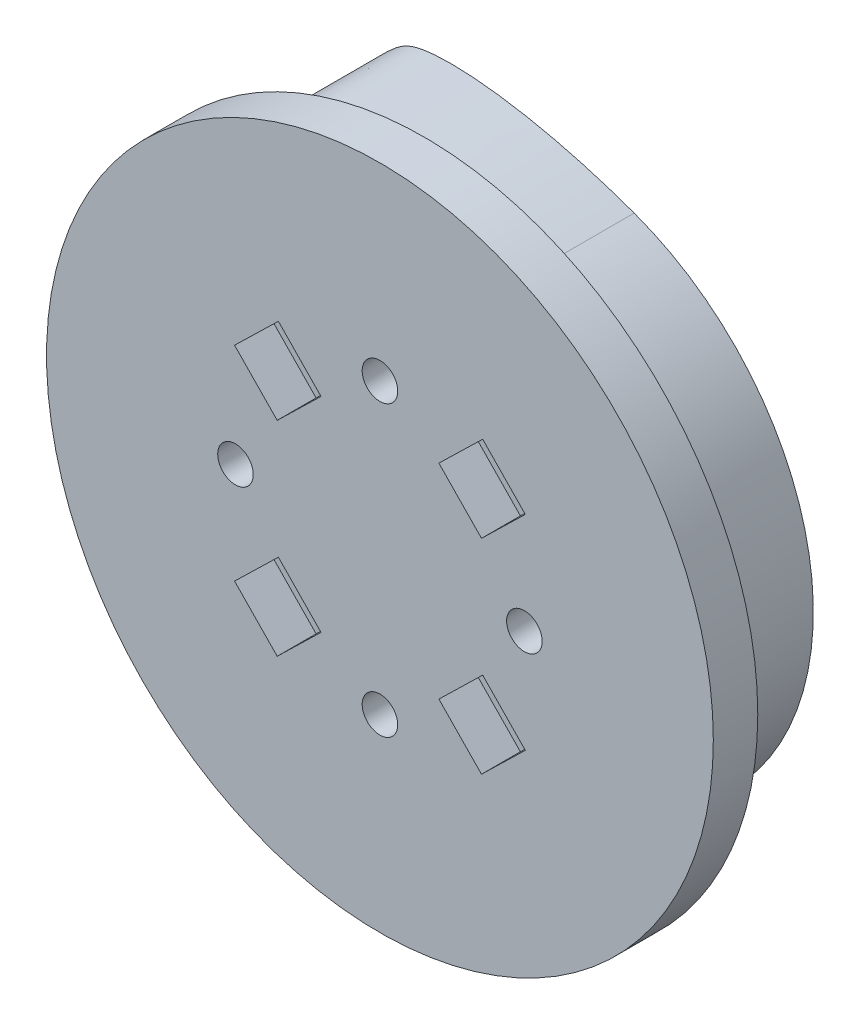
SolidWorks part; units mm, degrees
ref_plane "Front Plane" through (0, 0, 0) normal (1, 0, 0) x (0, 1, 0)
ref_plane "Top Plane" through (0, 0, 0) normal (0, 0, 1) x (0, 1, 0)
ref_plane "Right Plane" through (0, 0, 0) normal (0, 1, 0) x (-1, 0, 0)
sketch "Sketch1" plane through (0, 0, 0) normal (0, 0, 1) x (0, 1, 0)
  circle A0 centre (0, 0) radius 21
  circle A1 centre (0, 0) radius 13 construction
  circle A2 centre (0, 13) radius 1.6
  circle A3 centre (0, 13) radius 2.85
  circle A4 centre (13, 0) radius 2.85
  circle A5 centre (13, 0) radius 1.6
  circle A6 centre (0, -13) radius 2.85
  circle A7 centre (0, -13) radius 1.6
  circle A8 centre (-13, 0) radius 2.85
  circle A9 centre (-13, 0) radius 1.6
  point P19 (0, 0)
  dimension "D1" = 42
  dimension "D2" = 26
  dimension "D3" = 3.2
  dimension "D4" = 5.7
  dimension "D5" = 4
extrude "Boss-Extrude1" add sketch "Sketch1" along normal blind 10.5 contours A0 A8 A6 A4 A3 | A8 A9 | A3 A2 | A4 A5 | A6 A7 region at (0, 0, 0) region at (-13, -2.7694, 0) region at (0, 10.2306, 0) region at (13, -2.7694, 0) region at (0, -15.7694, 0)
sketch "Sketch2" plane through (0, 0, 0) normal (0, 0, -1) x (1, 0, 0)
  line L0 (0, 0) -> (0, 28.5) construction
  line L1 (0, 0) -> (-12.0446, -25.8298) construction
  line L2 (0, 0) -> (-26.7812, -9.7476) construction
  line L3 (0, 0) -> (9.7476, -26.7812) construction
  line L4 (-13.7052, -25.0554) -> (-49.9575, -8.1507) construction
  line L5 (-8.9203, -47.1248) -> (-49.9627, 65.6383) construction
  line L6 (47.1248, -8.9203) -> (-65.6383, -49.9627) construction
  circle A0 centre (0, 0) radius 28.5 construction
  circle A1 centre (0, 0) radius 24.5
  spline S0 degree 3 poles (-23.0225, -8.3795) (-19.9443, -16.8367) (-14.7237, -24.6248) (-9.3995, -27.1075) (-0.0777, -26.1007) (8.3795, -23.0225) knots 0 0 0 0 0.45 0.55 1 1 1 1
  circle M5 centre (0, 0) radius 21
  dimension "D1" = 57
  dimension "D2" = 49
  dimension "D6" = 20
  dimension "D7" = 30
  dimension "D8" = 30
  dimension "D3" = 205
  dimension "D4" = 45
  dimension "D5" = 45
  dimension "D9" = 90
  dimension "D10" = 90
  dimension "D11" = 90
extrude "Boss-Extrude3" add sketch "Sketch2" against normal up to surface (10.5 mm away) contours A1 M5 | A1 S0 region at (19.5016, 13.6552, 0) region at (-10.6097, 22.7453, 0) up to face at (21, 0, 10.5)
sketch "Sketch4" plane through (0, 0, 10.5) normal (0, 0, 1) x (1, 0, 0)
  circle A0 centre (0, 0) radius 30
  circle A5 centre (-13, 0) radius 1.6
  circle A6 centre (0, 13) radius 1.6
  circle A7 centre (13, 0) radius 1.6
  circle A8 centre (0, -13) radius 1.6
  dimension "D1" = 60
extrude "Boss-Extrude5" add sketch "Sketch4" along normal blind 4
sketch "Sketch3" plane through (0, 0, 0) normal (0, 0, -1) x (1, 0, 0)
  circle A0 centre (0, 0) radius 21
  circle A5 centre (-13, 0) radius 1.6
  circle A6 centre (0, 13) radius 1.6
  circle A7 centre (13, 0) radius 1.6
  circle A8 centre (0, -13) radius 1.6
  dimension "D1" = 42
extrude "Boss-Extrude4" add sketch "Sketch3" along normal blind 0.5
sketch "Sketch6" plane through (0, 0, -0.5) normal (0, 0, -1) x (1, 0, 0)
  line L0 (15.75, -2.75) -> (10.25, -2.75)
  line L1 (-2.75, 15.75) -> (2.75, 15.75)
  line L2 (-2.75, 15.75) -> (-2.75, 10.25)
  line L3 (-2.75, 10.25) -> (2.75, 10.25)
  line L4 (2.75, 15.75) -> (2.75, 10.25)
  line L5 (-2.75, 15.75) -> (2.75, 10.25) construction
  line L6 (-2.75, 10.25) -> (2.75, 15.75) construction
  line L7 (10.25, 2.75) -> (10.25, -2.75)
  line L8 (15.75, 2.75) -> (10.25, 2.75)
  line L9 (15.75, 2.75) -> (15.75, -2.75)
  line L10 (15.75, 2.75) -> (10.25, -2.75) construction
  line L11 (10.25, 2.75) -> (15.75, -2.75) construction
  line L12 (-2.75, -15.75) -> (-2.75, -10.25)
  line L13 (2.75, -10.25) -> (-2.75, -10.25)
  line L14 (2.75, -15.75) -> (2.75, -10.25)
  line L15 (2.75, -15.75) -> (-2.75, -15.75)
  line L16 (2.75, -15.75) -> (-2.75, -10.25) construction
  line L17 (2.75, -10.25) -> (-2.75, -15.75) construction
  line L18 (-15.75, 2.75) -> (-10.25, 2.75)
  line L19 (-10.25, -2.75) -> (-10.25, 2.75)
  line L20 (-15.75, -2.75) -> (-10.25, -2.75)
  line L21 (-15.75, -2.75) -> (-15.75, 2.75)
  line L22 (-15.75, -2.75) -> (-10.25, 2.75) construction
  line L23 (-10.25, -2.75) -> (-15.75, 2.75) construction
  point P0 (0, 13)
  point P21 (0, 0)
  dimension "D1" = 5.5
  dimension "D2" = 5.5
extrude "Cut-Extrude2" cut sketch "Sketch6" against normal offset from surface (3.5 mm away) 11.5 up to face at (14.6, 0, 14.5)
sketch "Sketch7" plane through (0, 0, 14.5) normal (0, 0, 1) x (1, 0, 0)
  line L0 (0, 0) -> (9.1924, 9.1924) construction
  line L1 (9.2456, 13.0807) -> (5.3041, 9.2465)
  line L2 (9.2456, 13.0807) -> (13.0807, 9.1383)
  line L3 (5.3041, 9.2465) -> (9.1392, 5.3041)
  line L4 (13.0807, 9.1383) -> (9.1392, 5.3041)
  line L5 (9.2456, 13.0807) -> (9.1392, 5.3041) construction
  line L6 (5.3041, 9.2465) -> (13.0807, 9.1383) construction
  line L7 (9.1383, -13.0807) -> (5.3041, -9.1392)
  line L8 (9.2465, -5.3041) -> (5.3041, -9.1392)
  line L9 (13.0807, -9.2456) -> (9.2465, -5.3041)
  line L10 (13.0807, -9.2456) -> (9.1383, -13.0807)
  line L11 (13.0807, -9.2456) -> (5.3041, -9.1392) construction
  line L12 (9.2465, -5.3041) -> (9.1383, -13.0807) construction
  line L13 (-13.0807, -9.1383) -> (-9.1392, -5.3041)
  line L14 (-5.3041, -9.2465) -> (-9.1392, -5.3041)
  line L15 (-9.2456, -13.0807) -> (-5.3041, -9.2465)
  line L16 (-9.2456, -13.0807) -> (-13.0807, -9.1383)
  line L17 (-9.2456, -13.0807) -> (-9.1392, -5.3041) construction
  line L18 (-5.3041, -9.2465) -> (-13.0807, -9.1383) construction
  line L19 (-9.1383, 13.0807) -> (-5.3041, 9.1392)
  line L20 (-9.2465, 5.3041) -> (-5.3041, 9.1392)
  line L21 (-13.0807, 9.2456) -> (-9.2465, 5.3041)
  line L22 (-13.0807, 9.2456) -> (-9.1383, 13.0807)
  line L23 (-13.0807, 9.2456) -> (-5.3041, 9.1392) construction
  line L24 (-9.2465, 5.3041) -> (-9.1383, 13.0807) construction
  circle A0 centre (0, 0) radius 13 construction
  circle A1 centre (9.1924, 9.1924) radius 1.6
  circle A10 centre (9.1924, -9.1924) radius 1.6
  circle A11 centre (-9.1924, -9.1924) radius 1.6
  circle A12 centre (-9.1924, 9.1924) radius 1.6
  point P18 (0, 0)
  point P34 (0, 0)
  dimension "D1" = 3.2
  dimension "D2" = 5.4988
  dimension "D3" = 5.5
extrude "Cut-Extrude3" cut sketch "Sketch7" against normal through all contours A1 | A12 | A11 | A10 region at (9.1924, 9.1924, 14.5) region at (9.1924, -9.1924, 14.5) region at (-9.1924, -9.1924, 14.5) region at (-9.1924, 9.1924, 14.5)
extrude "Cut-Extrude4" cut sketch "Sketch7<3>" against normal blind 3.5
sketch "Sketch7<3>" plane through (0, 0, 14.5) normal (0, 0, 1) x (1, 0, 0) same geometry as "Sketch7"
